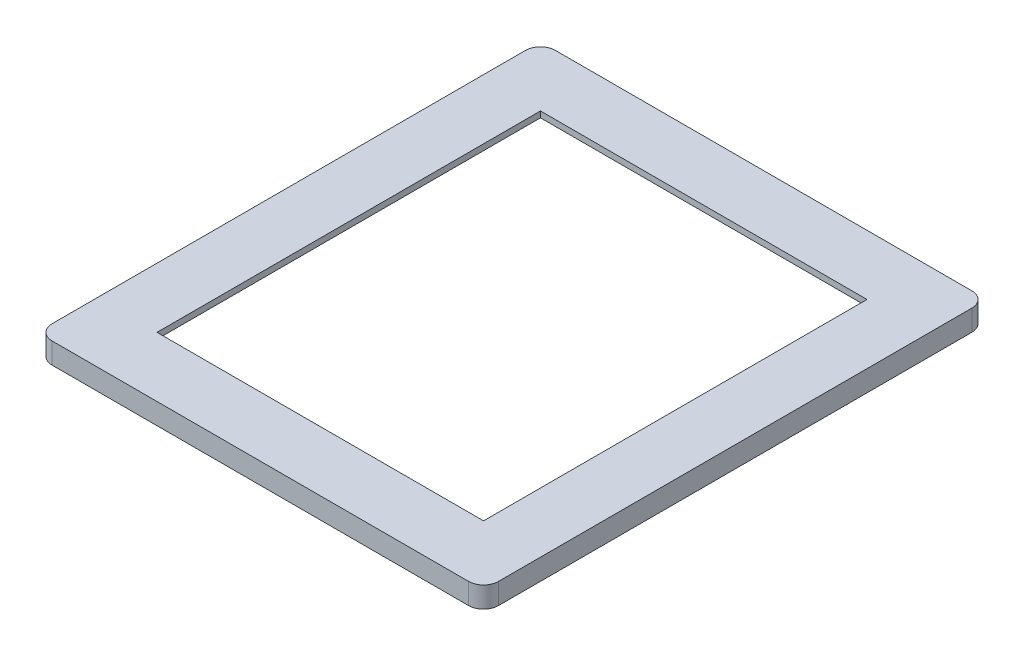
SolidWorks part; units mm, degrees
ref_plane "Front Plane" through (0, 0, 0) normal (0, 0, 1) x (1, 0, 0)
ref_plane "Top Plane" through (0, 0, 0) normal (0, 1, 0) x (1, 0, 0)
ref_plane "Right Plane" through (0, 0, 0) normal (1, 0, 0) x (0, 0, -1)
sketch "Sketch1" plane through (0, 0, 0) normal (0, 1, 0) x (1, 0, 0)
  line L0 (-122.389, 0) -> (137.7285, 0) construction
  line L1 (0, 82.8982) -> (0, -107.0496) construction
  line L2 (-71.312, 66.9817) -> (53.688, 66.9817)
  line L3 (53.688, 66.9817) -> (53.688, -77.0183)
  line L4 (53.688, -77.0183) -> (-71.312, -77.0183)
  line L5 (-71.312, -77.0183) -> (-71.312, 66.9817)
  line L6 (-83.312, 78.9817) -> (65.688, 78.9817)
  line L7 (65.688, 78.9817) -> (65.688, -89.0183)
  line L8 (65.688, -89.0183) -> (-83.312, -89.0183)
  line L9 (-83.312, -89.0183) -> (-83.312, 78.9817)
  dimension "D1" = 125
  dimension "D2" = 144
  dimension "D3" = 12
  dimension "D4" = 12
  dimension "D5" = 12
  dimension "D6" = 12
extrude "Boss-Extrude1" add sketch "Sketch1" along normal blind 7
fillet "Fillet1" radius 5 1 edges at (65.688, 3.5, 89.0183)
fillet "Fillet2" radius 5 1 edges at (-83.312, 3.5, 89.0183)
fillet "Fillet3" radius 5 1 edges at (-83.312, 3.5, -78.9817)
fillet "Fillet4" radius 5 1 edges at (65.688, 3.5, -78.9817)
sketch "Sketch4" plane through (0, 0, 0) normal (0, -1, 0) x (1, 0, 0)
  line L2 (-40.312, 80.0183) -> (-25.812, 80.0183)
  line L3 (-25.812, 80.0183) -> (-25.812, 84.5183)
  line L4 (-25.812, 84.5183) -> (-60.812, 84.5183)
  line L5 (-60.812, 84.5183) -> (-60.812, 80.0183)
  line L6 (-60.812, 80.0183) -> (-46.312, 80.0183)
  line L9 (22.688, 77.0183) -> (22.688, 80.0183)
  line L10 (53.688, 77.0183) -> (-71.312, 77.0183) construction
  line L11 (-46.312, 78.5183) -> (-40.312, 78.5183) construction
  line L14 (-43.312, 77.0183) -> (-8.812, 77.0183) construction
  line L15 (-46.312, 80.0183) -> (-46.312, 77.0183)
  line L16 (-46.312, 77.0183) -> (-40.312, 77.0183)
  line L17 (-40.312, 77.0183) -> (-40.312, 80.0183)
  line L18 (-8.812, 79.5665) -> (-8.812, 74.4701) construction
  line L19 (22.688, 80.0183) -> (8.188, 80.0183)
  line L20 (8.188, 80.0183) -> (8.188, 84.5183)
  line L21 (8.188, 84.5183) -> (43.188, 84.5183)
  line L22 (43.188, 84.5183) -> (43.188, 80.0183)
  line L23 (43.188, 80.0183) -> (28.688, 80.0183)
  line L24 (28.688, 80.0183) -> (28.688, 77.0183)
  line L25 (28.688, 77.0183) -> (22.688, 77.0183)
  line L26 (53.688, 47.0183) -> (56.688, 47.0183)
  line L27 (56.688, 47.0183) -> (56.688, 66.5183)
  line L28 (56.688, 66.5183) -> (61.188, 66.5183)
  line L29 (61.188, 66.5183) -> (61.188, 21.5183)
  line L30 (61.188, 21.5183) -> (56.688, 21.5183)
  line L31 (56.688, 21.5183) -> (56.688, 41.0183)
  line L32 (56.688, 41.0183) -> (53.688, 41.0183)
  line L33 (53.688, 41.0183) -> (53.688, 47.0183)
  line L34 (53.688, -35.9817) -> (56.688, -35.9817)
  line L35 (56.688, -35.9817) -> (56.688, -13.9817)
  line L36 (56.688, -13.9817) -> (61.188, -13.9817)
  line L37 (61.188, -13.9817) -> (61.188, -63.9817)
  line L38 (61.188, -63.9817) -> (56.688, -63.9817)
  line L39 (56.688, -63.9817) -> (56.688, -41.9817)
  line L40 (56.688, -41.9817) -> (53.688, -41.9817)
  line L41 (53.688, -41.9817) -> (53.688, -35.9817)
  line L44 (43.188, -69.9817) -> (43.188, -74.4817)
  line L45 (43.188, -74.4817) -> (8.188, -74.4817)
  line L46 (8.188, -74.4817) -> (8.188, -69.9817)
  line L47 (8.188, -69.9817) -> (22.688, -69.9817)
  line L48 (22.688, -69.9817) -> (22.688, -66.9817)
  line L58 (-71.312, -41.9817) -> (-74.312, -41.9817)
  line L59 (-74.312, -41.9817) -> (-74.312, -63.9817)
  line L60 (-74.312, -63.9817) -> (-78.812, -63.9817)
  line L61 (-78.812, -63.9817) -> (-78.812, -13.9817)
  line L62 (-78.812, -13.9817) -> (-74.312, -13.9817)
  line L63 (-74.312, -13.9817) -> (-74.312, -35.9817)
  line L64 (-74.312, -35.9817) -> (-71.312, -35.9817)
  line L65 (-71.312, -35.9817) -> (-71.312, -41.9817)
  line L66 (-71.312, 41.0183) -> (-74.312, 41.0183)
  line L67 (-74.312, 41.0183) -> (-74.312, 21.5183)
  line L68 (-74.312, 21.5183) -> (-78.812, 21.5183)
  line L69 (-78.812, 21.5183) -> (-78.812, 66.5183)
  line L70 (-78.812, 66.5183) -> (-74.312, 66.5183)
  line L71 (-74.312, 66.5183) -> (-74.312, 47.0183)
  line L72 (-74.312, 47.0183) -> (-71.312, 47.0183)
  line L73 (-71.312, 47.0183) -> (-71.312, 41.0183)
  line L74 (22.688, -66.9817) -> (28.688, -66.9817)
  line L75 (28.688, -66.9817) -> (28.688, -69.9817)
  line L76 (28.688, -69.9817) -> (43.188, -69.9817)
  point P3 (-43.312, 77.0183)
  point P24 (-8.812, 77.0183)
  dimension "D1" = 6
  dimension "D2" = 3
  dimension "D3" = 35
  dimension "34.45" = 34.5
  dimension "D4" = 4.5
extrude "Cut-Extrude1" cut sketch "Sketch4" against normal blind 3
sketch "Sketch5" plane through (-724.6859, -915.5936, -1334.8866) normal (0, 1, 0) x (1, 0, 0)
sketch "Sketch6" plane through (0, 0, 0) normal (0, -1, 0) x (1, 0, 0)
  circle A0 centre (-76.5798, 82.286) radius 1.325
  circle A1 centre (58.9558, 82.286) radius 1.325
  circle A2 centre (58.9558, -72.2495) radius 1.325
  circle A3 centre (-76.5798, -72.2495) radius 1.325
  dimension "D1" = 2.65
  dimension "D2" = 2.65
  dimension "D3" = 2.65
  dimension "D4" = 2.65
extrude "Cut-Extrude2" cut sketch "Sketch6" against normal blind 4
sketch "Sketch7" plane through (0, 3, 0) normal (0, -1, 0) x (1, 0, 0)
  line L0 (53.688, -35.9817) -> (56.688, -35.9817)
  line L1 (56.688, -35.9817) -> (56.688, -30.9817)
  line L2 (56.688, -13.9817) -> (56.688, -35.9817) construction
  line L3 (56.688, -30.9817) -> (61.188, -30.9817)
  line L4 (61.188, -63.9817) -> (61.188, -13.9817) construction
  line L5 (61.188, -30.9817) -> (61.188, -46.9817)
  line L6 (61.188, -63.9817) -> (61.188, -13.9817) construction
  line L7 (61.188, -46.9817) -> (56.688, -46.9817)
  line L8 (56.688, -41.9817) -> (56.688, -63.9817) construction
  line L9 (56.688, -46.9817) -> (56.688, -41.9817)
  line L10 (56.688, -41.9817) -> (53.688, -41.9817)
  line L11 (53.688, -41.9817) -> (53.688, -35.9817)
  line L12 (53.688, 47.0183) -> (56.688, 47.0183)
  line L13 (56.688, 47.0183) -> (56.688, 52.0183)
  line L14 (56.688, 52.0183) -> (61.188, 52.0183)
  line L15 (61.188, 52.0183) -> (61.188, 36.0183)
  line L16 (61.188, 36.0183) -> (56.688, 36.0183)
  line L17 (56.688, 36.0183) -> (56.688, 41.0183)
  line L18 (56.688, 41.0183) -> (53.688, 41.0183)
  line L19 (53.688, 41.0183) -> (53.688, 47.0183)
  line L20 (28.688, 77.0183) -> (28.688, 80.0183)
  line L21 (28.688, 80.0183) -> (33.688, 80.0183)
  line L22 (28.688, 80.0183) -> (43.188, 80.0183) construction
  line L23 (33.688, 80.0183) -> (33.688, 84.5183)
  line L24 (43.188, 84.5183) -> (8.188, 84.5183) construction
  line L25 (33.688, 84.5183) -> (17.688, 84.5183)
  line L26 (17.688, 84.5183) -> (17.688, 80.0183)
  line L27 (8.188, 80.0183) -> (22.688, 80.0183) construction
  line L28 (17.688, 80.0183) -> (22.688, 80.0183)
  line L29 (22.688, 80.0183) -> (22.688, 77.0183)
  line L30 (22.688, 77.0183) -> (28.688, 77.0183)
  line L31 (-40.312, 77.0183) -> (-40.312, 80.0183)
  line L32 (-40.312, 80.0183) -> (-35.312, 80.0183)
  line L33 (-35.312, 80.0183) -> (-35.312, 84.5183)
  line L34 (-35.312, 84.5183) -> (-51.312, 84.5183)
  line L35 (-51.312, 84.5183) -> (-51.312, 80.0183)
  line L36 (-51.312, 80.0183) -> (-46.312, 80.0183)
  line L37 (-46.312, 80.0183) -> (-46.312, 77.0183)
  line L38 (-46.312, 77.0183) -> (-40.312, 77.0183)
  line L39 (-71.312, 47.0183) -> (-74.312, 47.0183)
  line L40 (-74.312, 47.0183) -> (-74.312, 52.0183)
  line L41 (-74.312, 47.0183) -> (-74.312, 66.5183) construction
  line L42 (-74.312, 52.0183) -> (-78.812, 52.0183)
  line L43 (-78.812, 66.5183) -> (-78.812, 21.5183) construction
  line L44 (-78.812, 52.0183) -> (-78.812, 36.0183)
  line L45 (-78.812, 66.5183) -> (-78.812, 21.5183) construction
  line L46 (-78.812, 36.0183) -> (-74.312, 36.0183)
  line L47 (-74.312, 21.5183) -> (-74.312, 41.0183) construction
  line L48 (-74.312, 36.0183) -> (-74.312, 41.0183)
  line L49 (-74.312, 41.0183) -> (-71.312, 41.0183)
  line L50 (-71.312, 41.0183) -> (-71.312, 47.0183)
  line L51 (-71.312, -35.9817) -> (-74.312, -35.9817)
  line L52 (-74.312, -35.9817) -> (-74.312, -30.9817)
  line L53 (-74.312, -35.9817) -> (-74.312, -13.9817) construction
  line L54 (-74.312, -30.9817) -> (-78.812, -30.9817)
  line L55 (-78.812, -13.9817) -> (-78.812, -63.9817) construction
  line L56 (-78.812, -30.9817) -> (-78.812, -46.9817)
  line L57 (-78.812, -13.9817) -> (-78.812, -63.9817) construction
  line L58 (-78.812, -46.9817) -> (-74.312, -46.9817)
  line L59 (-74.312, -63.9817) -> (-74.312, -41.9817) construction
  line L60 (-74.312, -46.9817) -> (-74.312, -41.9817)
  line L61 (-74.312, -41.9817) -> (-71.312, -41.9817)
  line L62 (-71.312, -41.9817) -> (-71.312, -35.9817)
  line L74 (22.688, -66.9817) -> (22.688, -69.9817)
  line L75 (22.688, -69.9817) -> (17.688, -69.9817)
  line L76 (22.688, -69.9817) -> (8.188, -69.9817) construction
  line L77 (17.688, -69.9817) -> (17.688, -74.4817)
  line L78 (8.188, -74.4817) -> (43.188, -74.4817) construction
  line L79 (17.688, -74.4817) -> (33.688, -74.4817)
  line L80 (33.688, -74.4817) -> (33.688, -69.9817)
  line L81 (43.188, -69.9817) -> (28.688, -69.9817) construction
  line L82 (33.688, -69.9817) -> (28.688, -69.9817)
  line L83 (28.688, -69.9817) -> (28.688, -66.9817)
  line L84 (28.688, -66.9817) -> (22.688, -66.9817)
  dimension "D1" = 5
  dimension "D2" = 5
  dimension "D3" = 5
  dimension "D4" = 5
extrude "Cut-Extrude3" cut sketch "Sketch7" against normal blind 2
sketch "Sketch8" plane through (0, 7, 0) normal (0, 1, 0) x (1, 0, 0)
  line L0 (-71.312, 66.9817) -> (-71.312, -77.0183)
  line L1 (-71.312, -77.0183) -> (53.688, -77.0183)
  line L2 (53.688, -77.0183) -> (53.688, 66.9817)
  line L3 (53.688, 66.9817) -> (-71.312, 66.9817)
  line L4 (-63.312, 58.9817) -> (-63.312, -69.0183)
  line L5 (-63.312, -69.0183) -> (45.688, -69.0183)
  line L6 (45.688, -69.0183) -> (45.688, 58.9817)
  line L7 (45.688, 58.9817) -> (-63.312, 58.9817)
  dimension "D1" = 8
  dimension "D2" = 8
  dimension "D3" = 8
  dimension "D4" = 8
extrude "Boss-Extrude2" add sketch "Sketch8" against normal blind 2
fillet "Fillet5" radius 3 6 edges at (56.688, 2.5, -41.9817) (56.688, 2.5, -35.9817) (56.688, 1.5, -13.9817) (61.188, 1.5, -13.9817) (56.688, 1.5, -63.9817) (61.188, 1.5, -63.9817)
fillet "Fillet7" radius 3 36 edges at (-78.812, 1.5, -13.9817) (-74.312, 1.5, -13.9817) (-78.812, 1.5, -63.9817) (-74.312, 1.5, -63.9817) (-74.312, 2.5, -35.9817) (-74.312, 2.5, -41.9817) (-78.812, 1.5, 66.5183) (-74.312, 1.5, 66.5183) (-78.812, 1.5, 21.5183) (-74.312, 1.5, 21.5183) (-74.312, 2.5, 41.0183) (-74.312, 2.5, 47.0183) (-46.312, 2.5, 80.0183) (-40.312, 2.5, 80.0183) (-25.812, 1.5, 84.5183) (-25.812, 1.5, 80.0183) (-60.812, 1.5, 84.5183) (-60.812, 1.5, 80.0183) (28.688, 2.5, 80.0183) (43.188, 1.5, 80.0183) (43.188, 1.5, 84.5183) (8.188, 1.5, 84.5183) (8.188, 1.5, 80.0183) (22.688, 2.5, 80.0183) (61.188, 1.5, 66.5183) (61.188, 1.5, 21.5183) (56.688, 1.5, 21.5183) (56.688, 2.5, 41.0183) (56.688, 2.5, 47.0183) (56.688, 1.5, 66.5183) (43.188, 1.5, -74.4817) (43.188, 1.5, -69.9817) (28.688, 2.5, -69.9817) (8.188, 1.5, -74.4817) (8.188, 1.5, -69.9817) (22.688, 2.5, -69.9817)
